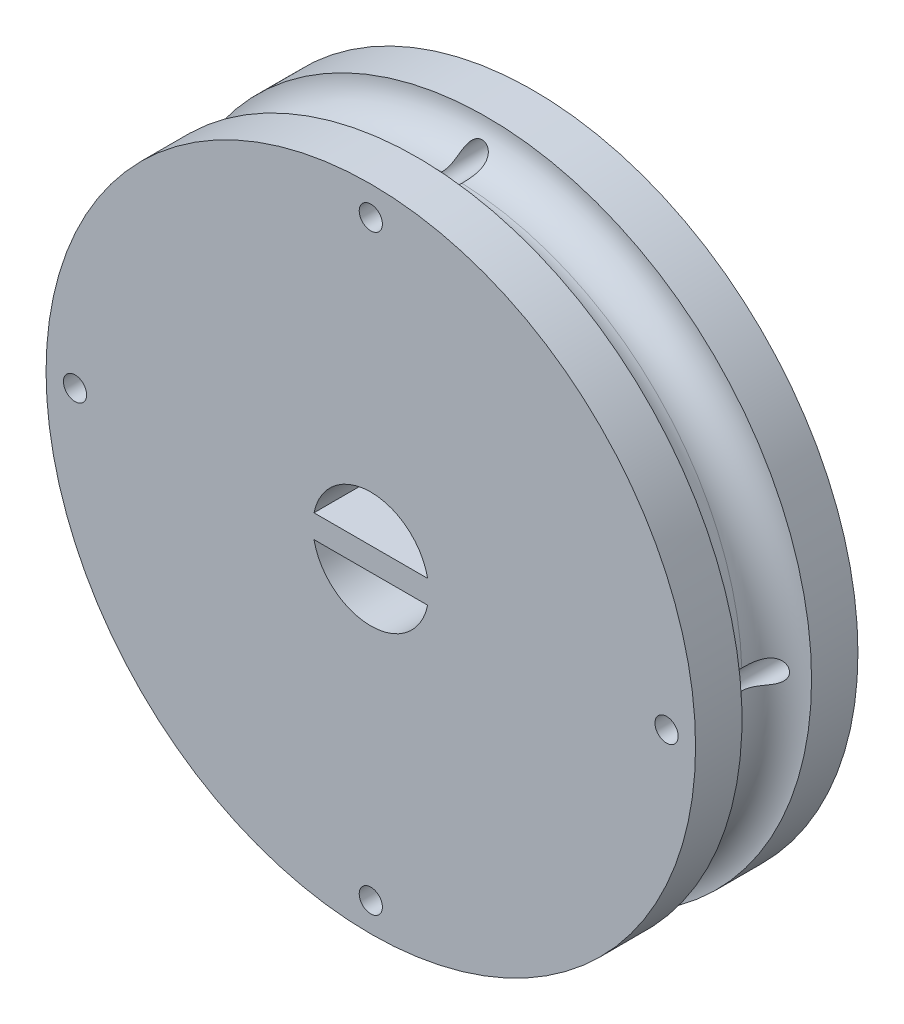
SolidWorks part; units mm, degrees
ref_plane "Front Plane" through (0, 0, 0) normal (0, 0, 1) x (1, 0, 0)
ref_plane "Top Plane" through (0, 0, 0) normal (0, 1, 0) x (1, 0, 0)
ref_plane "Right Plane" through (0, 0, 0) normal (1, 0, 0) x (0, 0, -1)
sketch "Sketch1" plane through (0, 0, 0) normal (0, 0, 1) x (1, 0, 0)
  circle A0 centre (0, 0) radius 14
extrude "Boss-Extrude1" add sketch "Sketch1" along normal blind 7
sketch "Sketch3" plane through (0, 0, 0) normal (0, 0, -1) x (-1, 0, 0)
  circle A0 centre (0, 0) radius 2.5
extrude "Cut-Extrude1" cut sketch "Sketch3" against normal through all
sketch "Sketch4" plane through (0, 0, 7) normal (0, 0, 1) x (1, 0, 0)
  line L1 (-2.5, 0.5) -> (2.5, 0.5)
  line L2 (-2.5, 0.5) -> (-2.5, -0.5)
  line L3 (-2.5, -0.5) -> (2.5, -0.5)
  line L4 (2.5, 0.5) -> (2.5, -0.5)
  dimension "D1" = 5
  dimension "D2" = 1
  dimension "D3" = 0.5
  dimension "D4" = 2.5
extrude "Boss-Extrude2" add sketch "Sketch4" against normal blind 2
sketch "Sketch5" plane through (0, 0, 0) normal (0, 0, -1) x (-1, 0, 0)
  circle A0 centre (0, 0) radius 3.5
  circle A1 centre (0, 0) radius 12
extrude "Cut-Extrude2" cut sketch "Sketch5" against normal blind 5
sketch "Sketch6" plane through (0, 0, 0) normal (0, 0, -1) x (-1, 0, 0)
  line L1 (-3.5, 1.25) -> (3.5, 1.25)
  line L2 (-3.5, 1.25) -> (-3.5, -1.25)
  line L3 (-3.5, -1.25) -> (3.5, -1.25)
  line L4 (3.5, 1.25) -> (3.5, -1.25)
  dimension "D1" = 1.25
  dimension "D2" = 3.5
extrude "Cut-Extrude3" cut sketch "Sketch6" against normal blind 5
sketch "Sketch7" plane through (0, 0, 0) normal (0, 0, -1) x (-1, 0, 0)
  circle A0 centre (0, 0) radius 14
  circle A1 centre (0, 0) radius 12.5
extrude "Cut-Extrude4" cut sketch "Sketch7" against normal blind 5
sketch "Sketch8" plane through (0, 0, 0) normal (0, 0, 1) x (1, 0, 0)
  circle A0 centre (0, 0) radius 14
  circle A1 centre (0, 0) radius 12.5
extrude "Boss-Extrude3" add sketch "Sketch8" along normal blind 2
fillet "Fillet1" radius 1.5 2 edges at (-12.5, 0, 5) (12.5, 0, 2)
sketch "Sketch9" plane through (0, 0, 0) normal (0, 0, -1) x (-1, 0, 0)
  circle A0 centre (-12.75, 0) radius 0.5
  circle A1 centre (12.75, 0) radius 0.5
  circle A2 centre (0, 12.75) radius 0.5
  circle A3 centre (0, -12.75) radius 0.5
  point P4 (12.9791, 0)
  point P7 (0, 13.472)
  point P11 (0, -13.2474)
  dimension "D1" = 12.75
  dimension "D2" = 12.75
  dimension "D3" = 12.75
  dimension "D4" = 12.75
extrude "Cut-Extrude7" cut sketch "Sketch9" against normal through all both and the other way through all contours A2 | A1 | A3 | A0
sketch "Sketch10" plane through (0, 0, 0) normal (0, 0, -1) x (-1, 0, 0)
  line L1 (-3.4287, 3.6232) -> (3.4457, 3.6232)
  line L2 (-3.4287, 3.6232) -> (-3.4287, -3.9227)
  line L3 (-3.4287, -3.9227) -> (3.4457, -3.9227)
  line L4 (3.4457, 3.6232) -> (3.4457, -3.9227)
extrude "Cut-Extrude8" cut sketch "Sketch10" against normal blind 2
